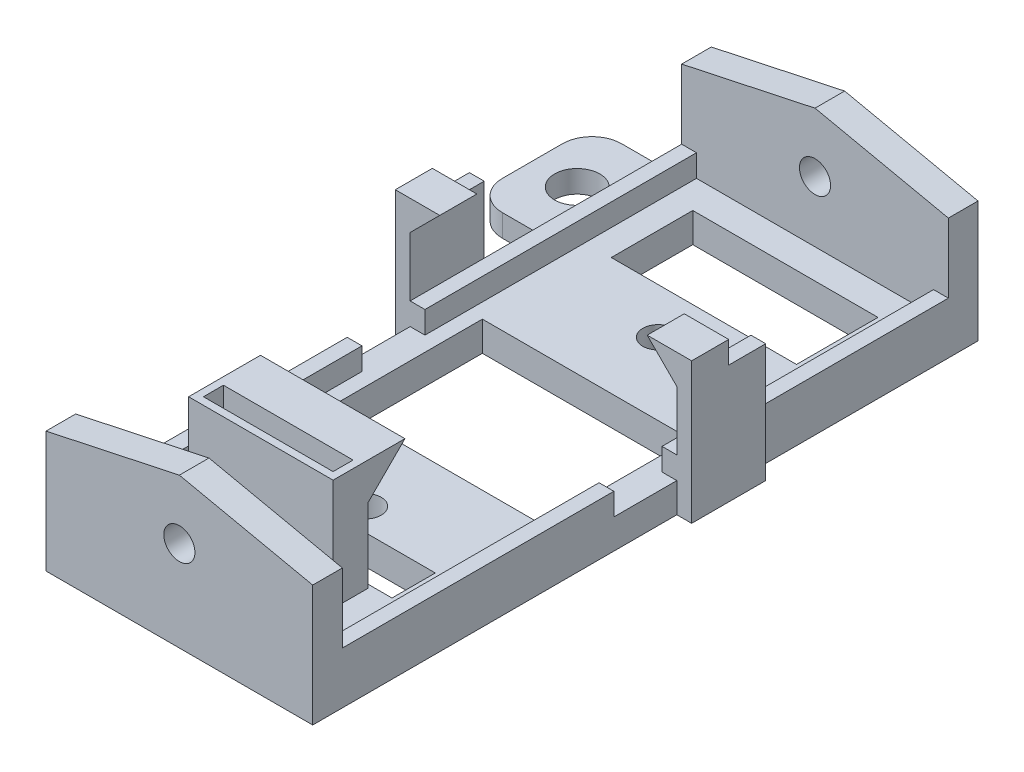
SolidWorks part; units mm, degrees
ref_plane "Front Plane" through (0, 0, 0) normal (0, 0, 1) x (1, 0, 0)
ref_plane "Top Plane" through (0, 0, 0) normal (0, 1, 0) x (1, 0, 0)
ref_plane "Right Plane" through (0, 0, 0) normal (1, 0, 0) x (0, 0, -1)
sketch "Sketch1" plane through (0, 0, 0) normal (0, 0, 1) x (1, 0, 0)
  line L2 (-40.4, 110) -> (0, 118.6383) construction
  line L3 (-18, 114.7896) -> (0, 114.7896)
  line L4 (0, 114.7896) -> (18, 114.7896)
  line L5 (0, 118.6383) -> (40.4, 110) construction
  line L11 (18, 114.7896) -> (18, 121.7896)
  line L12 (18, 121.7896) -> (16, 121.7896)
  line L13 (16, 121.7896) -> (16, 118.7896)
  line L14 (16, 118.7896) -> (-16, 118.7896)
  line L15 (-16, 118.7896) -> (-16, 121.7896)
  line L16 (-16, 121.7896) -> (-18, 121.7896)
  line L17 (-18, 121.7896) -> (-18, 114.7896)
  point P15 (0, 118.7896)
  dimension "D1" = 32
  dimension "D2" = 2
  dimension "D3" = 3
  dimension "D4" = 4
extrude "Boss-Extrude1" add sketch "Sketch1" along normal up to surface (89.8 mm away)
sketch "Sketch2" plane through (0, 114.7896, 0) normal (0, -1, 0) x (1, 0, 0)
  line L0 (18, 89.8) -> (18, 0) construction
  line L5 (-14, 54.9) -> (14, 54.9)
  line L6 (-14, 54.9) -> (-14, 34.9)
  line L7 (-14, 34.9) -> (14, 34.9)
  line L8 (14, 54.9) -> (14, 34.9)
  point P4 (0, 34.9)
  point P8 (18, 44.9)
  point P9 (14, 44.9)
  dimension "D1" = 4
  dimension "D2" = 20
extrude "Cut-Extrude1" cut sketch "Sketch2" against normal up to next
sketch "Sketch3" plane through (-18, 0, 0) normal (-1, 0, 0) x (0, 0, 1)
  line L0 (89.8, 121.7896) -> (0, 121.7896) construction
  line L1 (40.65, 118.7896) -> (49.15, 118.7896)
  line L2 (40.65, 118.7896) -> (40.65, 121.7896)
  line L3 (40.65, 121.7896) -> (49.15, 121.7896)
  line L4 (49.15, 118.7896) -> (49.15, 121.7896)
  line L5 (89.8, 118.7896) -> (0, 118.7896) construction
  point P9 (44.9, 121.7896)
  point P10 (44.9, 121.7896)
  dimension "D1" = 8.5
extrude "Cut-Extrude2" cut sketch "Sketch3" against normal through all
sketch "Sketch4" plane through (0, 118.7896, 0) normal (0, 1, 0) x (1, 0, 0)
  circle A0 centre (0, -25.15) radius 2.1 construction
  circle A1 centre (0, -64.65) radius 2.1 construction
  circle A2 centre (0, -25.15) radius 2.1
  circle A3 centre (0, -64.65) radius 2.1
extrude "Cut-Extrude3" cut sketch "Sketch4" against normal through all
ref_plane "Plane2" through (0, 0, 44.9) normal (0, 0, -1) x (-1, 0, 0)
sketch "Sketch5" plane through (0, 0, 0) normal (0, 0, 1) x (1, 0, 0)
  line L0 (-18, 114.7896) -> (-18, 131.1512)
  line L1 (-56.4, 122.9405) -> (0, 135) construction
  line L2 (-18, 131.1512) -> (0, 135)
  line L3 (0, 135) -> (18, 131.1512)
  line L4 (0, 135) -> (56.4, 122.9405) construction
  line L5 (18, 131.1512) -> (18, 114.7896)
  line L6 (18, 114.7896) -> (-18, 114.7896)
  line L7 (0.6273, 134.8659) -> (54.0273, 123.4479) construction
  line L8 (-54.0273, 123.4479) -> (-0.6273, 134.8659) construction
  circle A0 centre (0, 127) radius 2.1
  dimension "D1" = 4.2
  dimension "D2" = 8
extrude "Boss-Extrude2" add sketch "Sketch5" along normal blind 4
mirror "Mirror1" about plane through (0, 0, 44.9) normal (0, 0, -1) of "Boss-Extrude2"
sketch "Sketch6" plane through (0, 118.7896, 0) normal (0, 1, 0) x (1, 0, 0)
  line L1 (12.5, -19) -> (-12.5, -19)
  line L2 (12.5, -19) -> (12.5, -8)
  line L3 (12.5, -8) -> (-12.5, -8)
  line L4 (-12.5, -19) -> (-12.5, -8)
  point P4 (0, -8)
  dimension "D1" = 11
  dimension "D2" = 25
  dimension "D3" = 8
extrude "Cut-Extrude4" cut sketch "Sketch6" against normal through all
sketch "Sketch8" plane through (0, 118.7896, 0) normal (0, 1, 0) x (1, 0, 0)
  line L0 (16, -85.8) -> (-16, -85.8) construction
  line L1 (8.75, -77.8) -> (-8.75, -77.8)
  line L2 (8.75, -77.8) -> (8.75, -75.1)
  line L3 (8.75, -75.1) -> (-8.75, -75.1)
  line L4 (-8.75, -77.8) -> (-8.75, -75.1)
  line L6 (9.75, -74.1) -> (-9.75, -74.1)
  line L7 (-9.75, -78.8) -> (-9.75, -74.1)
  line L8 (9.75, -78.8) -> (-9.75, -78.8)
  line L9 (9.75, -78.8) -> (9.75, -74.1)
  point P6 (0, -85.8)
  point P7 (0, -77.8)
  dimension "D1" = 8
  dimension "D2" = 2.7
  dimension "D3" = 17.5
  dimension "D4" = 1
extrude "Boss-Extrude3" add sketch "Sketch8" along normal blind 15
sketch "Sketch9" plane through (-9.75, 0, 0) normal (-1, 0, 0) x (0, 0, 1)
  line L0 (74.1, 128.7896) -> (69.1, 133.7896)
  line L1 (74.1, 133.7896) -> (74.1, 118.7896) construction
  line L2 (69.1, 133.7896) -> (74.1, 133.7896)
  line L3 (74.1, 133.7896) -> (74.1, 128.7896)
  dimension "D1" = 5
  dimension "D2" = 45
extrude "Boss-Extrude4" add sketch "Sketch9" against normal up to surface (19.5 mm away) up to face at (9.75, 126.2896, 76.45)
sketch "Sketch13" plane through (0, 118.7896, 0) normal (0, 1, 0) x (1, 0, 0)
  line L4 (-8.75, -77.8) -> (8.75, -77.8)
  line L5 (8.75, -77.8) -> (8.75, -75.1)
  line L6 (8.75, -75.1) -> (-8.75, -75.1)
  line L7 (-8.75, -75.1) -> (-8.75, -77.8)
  line L8 (-8.75, -77.8) -> (8.75, -77.8)
  line L9 (8.75, -77.8) -> (8.75, -75.1)
  line L10 (8.75, -75.1) -> (-8.75, -75.1)
  line L11 (-8.75, -75.1) -> (-8.75, -77.8)
  dimension "D1" = 0
extrude "Cut-Extrude5" cut sketch "Sketch13" against normal through all
sketch "Sketch10" plane through (0, 114.7896, 0) normal (0, 1, 0) x (1, 0, 0)
  line L0 (18, -40.65) -> (18, -4) construction
  line L1 (18, -40.65) -> (20, -40.65)
  line L2 (18, -40.65) -> (18, -30.65)
  line L3 (18, -30.65) -> (20, -30.65)
  line L4 (20, -40.65) -> (20, -30.65)
  line L5 (0, -1000) -> (0, 49000) construction
  line L6 (-18, -30.65) -> (-20, -30.65)
  line L7 (-18, -40.65) -> (-18, -30.65)
  line L8 (-18, -40.65) -> (-20, -40.65)
  line L9 (-20, -40.65) -> (-20, -30.65)
  dimension "D1" = 10
  dimension "D2" = 2
extrude "Boss-Extrude5" add sketch "Sketch10" along normal offset from surface (16 mm away) 3
sketch "Sketch12" plane through (0, 0, 40.65) normal (0, 0, 1) x (1, 0, 0)
  line L0 (20, 129.7896) -> (20, 133.7896)
  line L1 (20, 133.7896) -> (14, 133.7896)
  line L2 (14, 133.7896) -> (18, 129.7896)
  line L3 (18, 129.7896) -> (20, 129.7896)
  line L4 (-18, 133.7896) -> (18, 133.7896) construction
  line L5 (18, 114.7896) -> (18, 131.1512) construction
  line L6 (20, 130.7896) -> (20, 114.7896) construction
  line L7 (18, 130.7896) -> (18, 121.7896) construction
  line L8 (0, -868.0678) -> (0, 49131.9322) construction
  line L9 (-18, 129.7896) -> (-20, 129.7896)
  line L10 (-14, 133.7896) -> (-18, 129.7896)
  line L11 (-20, 133.7896) -> (-14, 133.7896)
  line L12 (-20, 129.7896) -> (-20, 133.7896)
  dimension "D1" = 45
  dimension "D2" = 6
extrude "Boss-Extrude6" add sketch "Sketch12" against normal blind 5
sketch "Sketch14" plane through (0, 114.7896, 0) normal (0, 1, 0) x (1, 0, 0)
  line L0 (-18, -30.65) -> (-18, -4) construction
  line L1 (-18, -4) -> (-30.1, -4)
  line L2 (-18, -4) -> (-18, -20.1)
  line L3 (-18, -20.1) -> (-30.1, -20.1)
  line L4 (-30.1, -4) -> (-30.1, -20.1)
  circle A0 centre (-24.05, -12.05) radius 3.05
  point P9 (-30.1, -12.05)
  point P10 (-24.05, -20.1)
  dimension "D1" = 6.1
  dimension "D2" = 3
  dimension "D3" = 5
extrude "Boss-Extrude7" add sketch "Sketch14" along normal blind 3
fillet "Fillet1" radius 4 2 edges at (-30.1, 116.2896, 4) (-30.1, 116.2896, 20.1)
chamfer "Chamfer1" distance 3 angle 45 2 edges at (-18, 116.2896, 20.1) (-18, 116.2896, 4)
sketch "Sketch16" plane through (0, 118.7896, 0) normal (0, 1, 0) x (1, 0, 0)
  line L0 (9.75, -74.1) -> (-9.75, -74.1) construction
  line L1 (-12.5, -67.75) -> (12.5, -67.75)
  line L2 (-12.5, -67.75) -> (-12.5, -73.6)
  line L3 (-12.5, -73.6) -> (12.5, -73.6)
  line L4 (12.5, -67.75) -> (12.5, -73.6)
  circle A1 centre (0, -64.65) radius 2.1 construction
  point P4 (0, 0)
  point P9 (0, 0)
  dimension "D1" = 0.5
  dimension "D2" = 1
extrude "Cut-Extrude6" cut sketch "Sketch16" against normal through all
equation "\"width\"= 24"
equation "\"thk\"= 3"
equation "\"holesize\"= 4.2"
equation "\"holedistance\"= ( 20 + 12 ) / 2"
equation "\"threaded_hole\"= 3.9"
equation "\"fillet_radius\"= 2"
equation "\"ground_clearance\"= 25"
equation "\"tire_thk\"= 3"
equation "\"innerwheel_diam\" = \"wheel_diam\"-2*\"tire_thk\""
equation "\"innerwheel_thk\"= 8"
equation "\"wheel_diam\"= 2*(\"width\"/2+\"ground_clearance\")"
equation "\"coloursensor_holesize\"= 2.65"
equation "\"hole_to_edge\" = 4"
equation "\"D1@Sketch5\"=\"holesize\""
